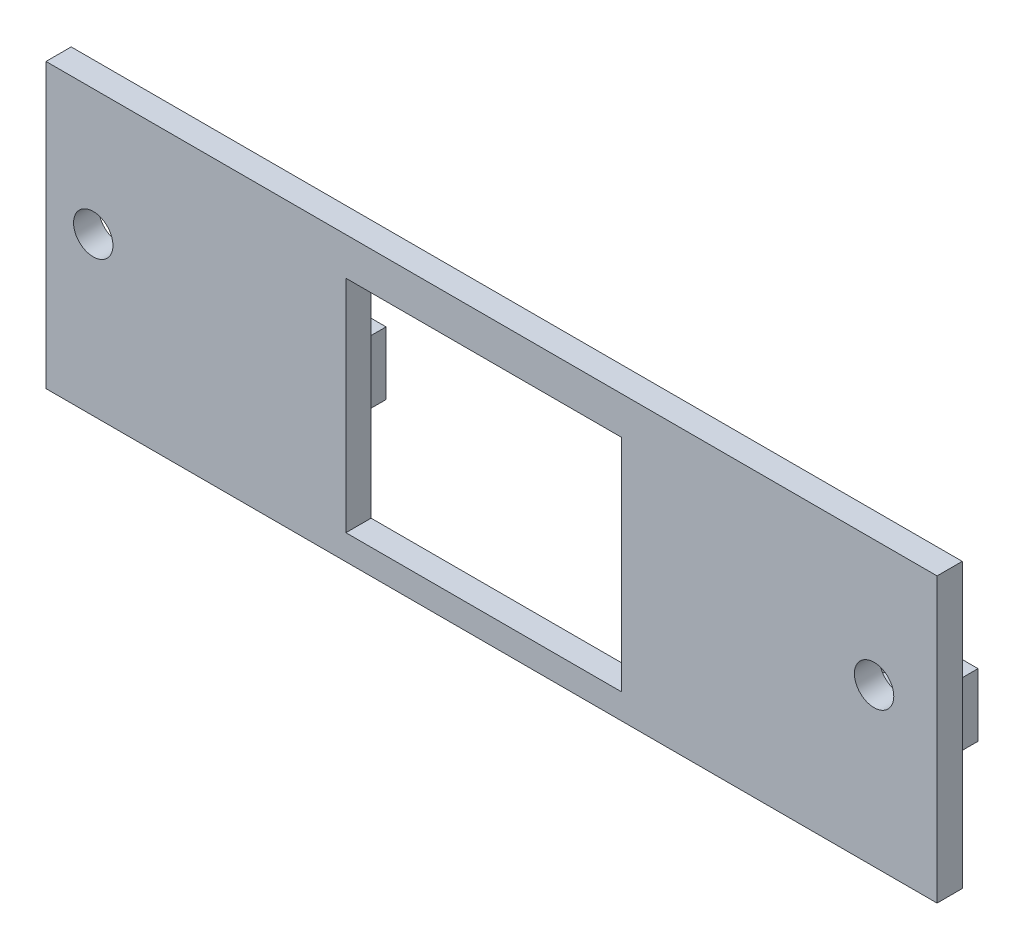
SolidWorks part; units mm, degrees
ref_plane "Front Plane" through (0, 0, 0) normal (0, 0, 1) x (1, 0, 0)
ref_plane "Top Plane" through (0, 0, 0) normal (0, 1, 0) x (1, 0, 0)
ref_plane "Right Plane" through (0, 0, 0) normal (1, 0, 0) x (0, 0, -1)
sketch "Sketch1" plane through (0, 0, 0) normal (0, 0, 1) x (1, 0, 0)
  line L0 (0, -55) -> (0, 55) construction
  line L1 (-28.8, 18) -> (28.8, 18)
  line L2 (-28.8, 18) -> (-28.8, 0)
  line L3 (-28.8, 0) -> (28.8, 0)
  line L4 (28.8, 18) -> (28.8, 0)
  line L5 (55, 0) -> (-55, 0) construction
  line L6 (-34.1699, 10) -> (46.6159, 10) construction
  circle A0 centre (-24.8, 10) radius 1.25
  circle A1 centre (24.8, 10) radius 1.25
  dimension "D1" = 57.6
  dimension "D2" = 18
  dimension "D3" = 28.8
  dimension "D4" = 0
  dimension "D5" = 10
  dimension "D6" = 24.8
  dimension "D7" = 24.8
extrude "Boss-Extrude1" add sketch "Sketch1" along normal blind 1.6
ref_plane "PCB top" through (0, 1.6, 0) normal (0, 1, 0) x (1, 0, 0)
sketch "Sketch7" plane through (0, 1.6, 0) normal (0, 1, 0) x (1, 0, 0)
  line L0 (0, -0.88) -> (0, 0.88) construction
  line L1 (-28.8, 75.2) -> (28.8, 75.2) construction
  line L2 (-28.8, 75.2) -> (-28.8, 0.2) construction
  line L3 (-28.8, 0.2) -> (28.8, 0.2) construction
  line L4 (28.8, 75.2) -> (28.8, 0.2) construction
  line L5 (-9.9, 0) -> (9.9, 0) construction
  line L6 (-22.8, 75.2) -> (-22.8, 0) construction
  line L7 (22.8, 75.2) -> (22.8, 0) construction
  line L9 (-22.8, 0) -> (-14.8, 0)
  line L10 (-22.8, 0) -> (-22.8, 7)
  line L11 (-22.8, 7) -> (-14.8, 7)
  line L12 (-14.8, 0) -> (-14.8, 7)
  line L13 (22.8, 0) -> (14.8, 0)
  line L14 (22.8, 0) -> (22.8, 7)
  line L15 (22.8, 7) -> (14.8, 7)
  line L16 (14.8, 0) -> (14.8, 7)
  circle A0 centre (-18.8, 4.2) radius 1.3
  circle A1 centre (18.8, 4.2) radius 1.3
  dimension "D14" = 2.6
  dimension "D15" = 2.6
  dimension "D1" = 28.8
  dimension "D2" = 28.8
  dimension "D3" = 0.2
  dimension "D4" = 75
  dimension "D5" = 6
  dimension "D6" = 6
  dimension "8" = 8
  dimension "D8" = 7
  dimension "D9" = 8
  dimension "D10" = 7
  dimension "D11" = 4
  dimension "D7" = 4
  dimension "D12" = 4
  dimension "D13" = 4
extrude "Boss-Extrude3" add sketch "Sketch7" along normal blind 4 separate body
sketch "Sketch8" plane through (0, 0, 0) normal (0, 0, 1) x (1, 0, 0)
  line L0 (0, -4.73) -> (0, 4.73) construction
  line L1 (-8.75, 15.6) -> (8.75, 15.6)
  line L2 (-8.75, 15.6) -> (-8.75, 1.6)
  line L3 (-8.75, 1.6) -> (8.75, 1.6)
  line L4 (8.75, 15.6) -> (8.75, 1.6)
  line L5 (4.73, 1.6) -> (-4.73, 1.6) construction
  dimension "D1" = 17.5
  dimension "D2" = 14
  dimension "D3" = 8.75
extrude "Cut-Extrude1" cut sketch "Sketch8" against normal through all both and the other way through all
combine bodies "Combine1" operation type add bodies to combine 106 108 107
fillet "Fillet1" radius 0.5 6 edges at (-14.8, 3.6, 0) (-22.8, 3.6, 0) (-18.8, 5.6, 0) (14.8, 3.6, 0) (22.8, 3.6, 0) (18.8, 5.6, 0)
sketch "Sketch9" plane through (-28.8, 0, 0) normal (-1, 0, 0) x (0, 0, 1)
  line L1 (1.6, 18) -> (0, 18)
  line L2 (1.6, 18) -> (1.6, 0)
  line L3 (1.6, 0) -> (0, 0)
  line L4 (0, 18) -> (0, 0)
extrude "MakeItFitReality" cut sketch "Sketch9" against normal blind 1
equation "\"D3@Sketch1\"=57.6/2"
equation "\"D1\"= 164 / 2"
equation "\"D1@Sketch7\"=57.6/2"
equation "\"D2@Sketch7\"=\"D1@Sketch7\""
equation "\"D9@Sketch7\"=\"8@Sketch7\""
equation "\"D10@Sketch7\"=\"D8@Sketch7\""
equation "\"D7@Sketch7\"=\"D11@Sketch7\""
equation "\"D15@Sketch7\"=\"D14@Sketch7\""
equation "\"D13@Sketch7\"=\"D12@Sketch7\""
